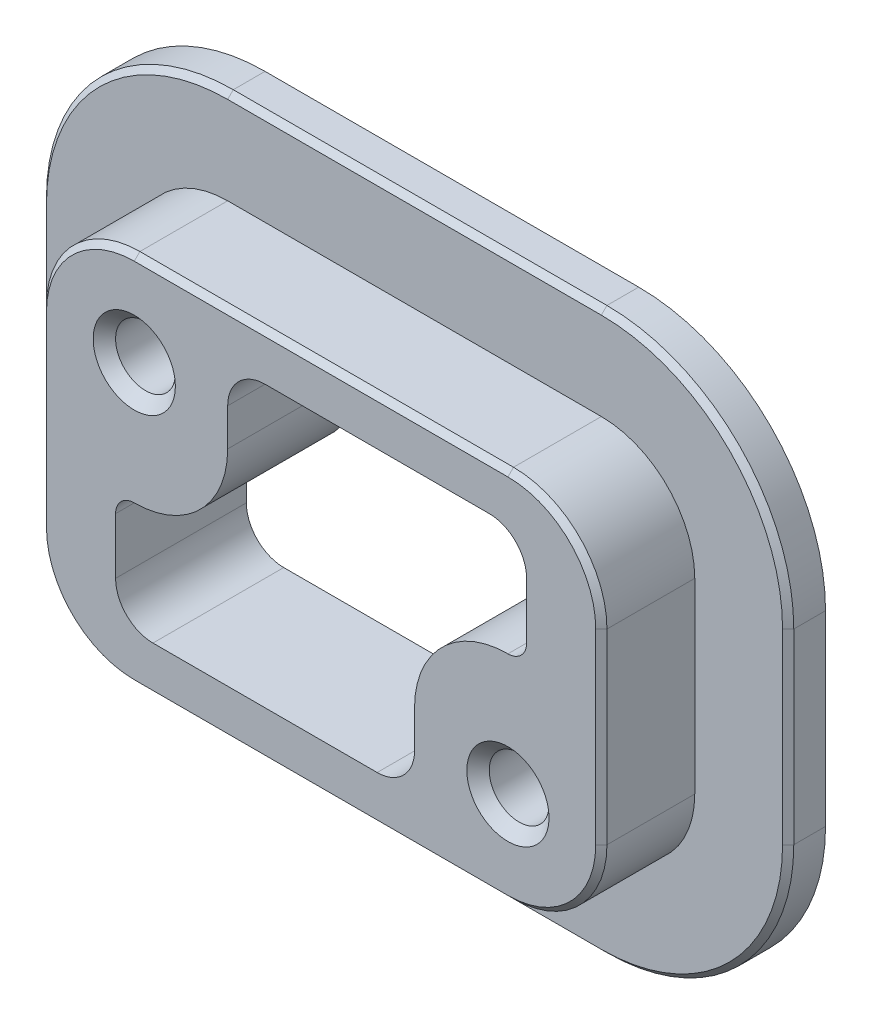
SolidWorks part; units mm, degrees
ref_plane "Ebene vorne" through (0, 0, 0) normal (0, 0, 1) x (1, 0, 0)
ref_plane "Ebene oben" through (0, 0, 0) normal (0, 1, 0) x (1, 0, 0)
ref_plane "Ebene rechts" through (0, 0, 0) normal (1, 0, 0) x (0, 0, -1)
sketch "Skizze1" plane through (0, 0, 0) normal (0, 0, 1) x (1, 0, 0)
  line L1 (15, 10) -> (-15, 10)
  line L2 (15, 10) -> (15, -10)
  line L3 (15, -10) -> (-15, -10)
  line L4 (-15, 10) -> (-15, -10)
  line L5 (15, 10) -> (-15, -10) construction
  line L6 (15, -10) -> (-15, 10) construction
  point P0 (0, 0)
  dimension "D1" = 20
  dimension "D2" = 30
extrude "Aufsatz-Linear austragen1" add sketch "Skizze1" along normal blind 5
fillet "Verrundung1" radius 5 4 edges at (-15, 10, 2.5) (-15, -10, 2.5) (15, -10, 2.5) (15, 10, 2.5)
sketch "Skizze2" plane through (0, 0, 0) normal (0, 0, -1) x (-1, 0, 0)
  line L8 (20, -5) -> (20, 5)
  line L9 (10, 15) -> (-10, 15)
  line L10 (-20, 5) -> (-20, -5)
  line L11 (-10, -15) -> (10, -15)
  line L12 (20, -5) -> (20, 5)
  line L13 (10, 15) -> (-10, 15)
  line L14 (-20, 5) -> (-20, -5)
  line L15 (-10, -15) -> (10, -15)
  arc A8 (20, 5) -> (10, 15) centre (10, 5) ccw
  arc A9 (-10, 15) -> (-20, 5) centre (-10, 5) ccw
  arc A10 (-20, -5) -> (-10, -15) centre (-10, -5) ccw
  arc A11 (10, -15) -> (20, -5) centre (10, -5) ccw
  arc A12 (20, 5) -> (10, 15) centre (10, 5) ccw
  arc A13 (-10, 15) -> (-20, 5) centre (-10, 5) ccw
  arc A14 (-20, -5) -> (-10, -15) centre (-10, -5) ccw
  arc A15 (10, -15) -> (20, -5) centre (10, -5) ccw
  dimension "D1" = 5
extrude "Aufsatz-Linear austragen2" add sketch "Skizze2" along normal blind 2
sketch "Skizze3" plane through (0, 0, 5) normal (0, 0, 1) x (1, 0, 0)
  circle A0 centre (-10, 5) radius 1.6
  circle A1 centre (10, -5) radius 1.6
  dimension "D1" = 3.2
extrude "Schnitt-Linear austragen1" cut sketch "Skizze3" against normal through all
sketch "Skizze4" plane through (0, 0, -2) normal (0, 0, -1) x (-1, 0, 0)
  line L1 (10, 8.4641) -> (7, 6.7321)
  line L2 (7, 6.7321) -> (7, 3.2679)
  line L3 (7, 3.2679) -> (10, 1.5359)
  line L4 (10, 1.5359) -> (13, 3.2679)
  line L5 (13, 3.2679) -> (13, 6.7321)
  line L6 (13, 6.7321) -> (10, 8.4641)
  line L7 (-10, -1.5359) -> (-13, -3.2679)
  line L8 (-13, -3.2679) -> (-13, -6.7321)
  line L9 (-13, -6.7321) -> (-10, -8.4641)
  line L10 (-10, -8.4641) -> (-7, -6.7321)
  line L11 (-7, -6.7321) -> (-7, -3.2679)
  line L12 (-7, -3.2679) -> (-10, -1.5359)
  circle A0 centre (10, 5) radius 3 construction
  circle A1 centre (-10, -5) radius 3 construction
  point P9 (10, 5)
  dimension "D1" = 6
extrude "Schnitt-Linear austragen2" cut sketch "Skizze4" against normal blind 3
sketch "Skizze5" plane through (0, 0, 5) normal (0, 0, 1) x (1, 0, 0)
  line L1 (5, 7.5) -> (-5, 7.5)
  line L2 (5, 1.5) -> (5, -7.5)
  line L3 (5, -7.5) -> (-5, -7.5)
  line L4 (-5, 7.5) -> (-5, -1.5)
  line L5 (5, 7.5) -> (-5, -7.5) construction
  line L6 (5, -7.5) -> (-5, 7.5) construction
  line L7 (-5, -7.5) -> (-11, -7.5)
  line L9 (-5, -1.5) -> (-11, -1.5)
  line L10 (-11, -7.5) -> (-11, -1.5)
  line L11 (5, 7.5) -> (11, 7.5)
  line L13 (5, 1.5) -> (11, 1.5)
  line L14 (11, 7.5) -> (11, 1.5)
  point P0 (0, 0)
  dimension "D1" = 15
  dimension "D2" = 10
  dimension "D3" = 6
  dimension "D4" = 6
extrude "Schnitt-Linear austragen3" cut sketch "Skizze5" against normal through all
fillet "Verrundung2" radius 5 2 edges at (5, 1.5, 1.5) (-5, -1.5, 1.5)
fillet "Verrundung3" radius 2 4 edges at (5, -7.5, 1.5) (-11, -7.5, 1.5) (-5, 7.5, 1.5) (11, 7.5, 1.5)
fillet "Verrundung4" radius 1 2 edges at (11, 1.5, 1.5) (-11, -1.5, 1.5)
chamfer "Fase1" distance 0.3 angle 45 16 edges at (0, -15, 0) (-17.0711, -12.0711, 0) (17.0711, -12.0711, 0) (-20, 0, 0) (20, 0, 0) (-17.0711, 12.0711, 0) (17.0711, 12.0711, 0) (0, 15, 0) (0, -10, 5) (13.5355, -8.5355, 5) (-13.5355, -8.5355, 5) (15, 0, 5) (-15, 0, 5) (13.5355, 8.5355, 5) (-13.5355, 8.5355, 5) (0, 10, 5)
chamfer "Fase2" distance 0.6 angle 45 2 edges at (-8.4, 5, 5) (11.6, -5, 5)
